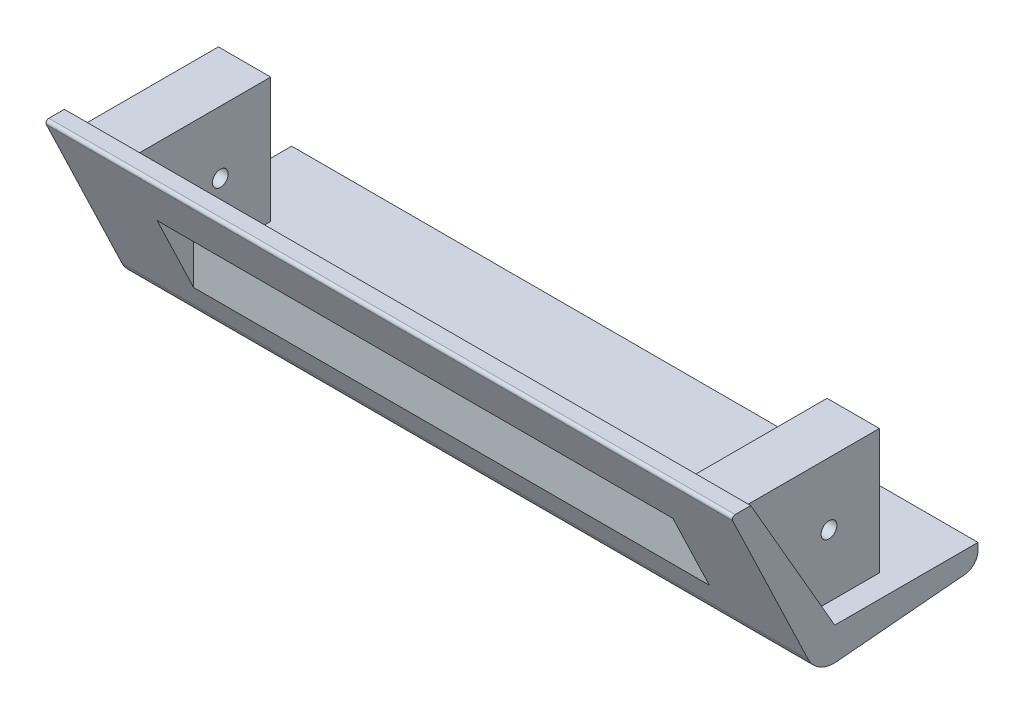
SolidWorks part; units mm, degrees
ref_plane "Front Plane" through (0, 0, 0) normal (0, 0, 1) x (1, 0, 0)
ref_plane "Top Plane" through (0, 0, 0) normal (0, 1, 0) x (1, 0, 0)
ref_plane "Right Plane" through (0, 0, 0) normal (1, 0, 0) x (0, 0, -1)
sketch "Sketch1" plane through (0, 0, 0) normal (1, 0, 0) x (0, 0, -1)
  line L0 (0, 0) -> (-29.3294, 50.8)
  line L1 (0, 0) -> (50, 0)
  line L2 (-29.3294, 50.8) -> (-36.3294, 50.8)
  line L3 (-36.3294, 50.8) -> (-6.2529, -12)
  line L4 (-6.2529, -12) -> (50, -7)
  line L5 (50, -7) -> (50, 0)
  line L6 (-6.2529, -12) -> (-6.2529, 0) construction
  line L7 (-12, 0) -> (0, 0) construction
  dimension "D1" = 50
  dimension "D2" = 60
  dimension "D3" = 50.8
  dimension "D4" = 7
  dimension "D5" = 7
  dimension "D6" = 12
extrude "Boss-Extrude2" add sketch "Sketch1" along normal mid plane 239.55
sketch "Sketch2" plane through (0, 0, 0) normal (0, 0, 1) x (1, 0, 0)
  line L0 (0, 0) -> (0, 50.8) construction
  line L5 (115.75, 47.625) -> (96.7, 47.625) construction
  line L6 (115.75, 47.625) -> (115.75, 3.175) construction
  line L11 (115.75, 3.175) -> (96.7, 3.175) construction
  line L12 (96.7, 47.625) -> (96.7, 3.175) construction
  line L14 (115.35, 47.225) -> (115.35, 3.575)
  line L15 (115.35, 3.575) -> (97.1, 3.575)
  line L28 (97.1, 47.225) -> (97.1, 3.575)
  line L29 (115.35, 47.225) -> (97.1, 47.225)
  line L30 (-96.7, 47.625) -> (-96.7, 3.175) construction
  line L31 (-115.75, 3.175) -> (-96.7, 3.175) construction
  line L32 (-115.75, 47.625) -> (-115.75, 3.175) construction
  line L33 (-115.75, 47.625) -> (-96.7, 47.625) construction
  line L34 (-115.35, 47.225) -> (-97.1, 47.225)
  line L35 (-97.1, 47.225) -> (-97.1, 3.575)
  line L36 (-115.35, 3.575) -> (-97.1, 3.575)
  line L37 (-115.35, 47.225) -> (-115.35, 3.575)
  line L39 (119.775, 0) -> (-119.775, 0) construction
  line L40 (119.775, 50.8) -> (-119.775, 50.8) construction
  line L41 (119.775, 0) -> (119.775, 50.8) construction
  dimension "D2" = 19.05
  dimension "D3" = 44.45
  dimension "D6" = 3.175
  dimension "D4" = 3.175
  dimension "D7" = 4.025
  dimension "D1" = 193.4
  dimension "D5" = 0.4
extrude "Boss-Extrude1" add sketch "Sketch2" along normal up to surface and the other way blind 20 up to face at (0, 25.4, 14.6647)
sketch "Sketch4" plane through (0, 0, 0) normal (1, 0, 0) x (0, 0, -1)
  line L1 (-26.7297, 30.7556) -> (-20, 34.641)
  line L2 (-36.3294, 50.8) -> (-6.2529, -12) construction
  line L3 (0, 0) -> (-29.3294, 50.8) construction
  line L4 (-20, 34.641) -> (-14, 24.2487)
  line L5 (-14, 24.2487) -> (-14, 4.176)
  line L8 (-26.7297, 30.7556) -> (-14, 4.176)
  dimension "D1" = 12
  dimension "D2" = 14
extrude "Cut-Extrude2" cut sketch "Sketch4" against normal mid plane 180
fillet "Fillet1" radius 10 1 edges at (0, -12, 6.2529)
fillet "Fillet2" radius 5 1 edges at (0, -7, -50)
fillet "Fillet3" radius 1 1 edges at (0, 50.8, 36.3294)
hole_wizard "M5 Clearance Hole1" positions "Sketch7" profile "Sketch6" hole size "M5" standard "ANSI Metric" end condition through all
sketch "Sketch7" plane through (115.35, 0, 0) normal (1, 0, 0) x (0, 0, -1)
  line L2 (20, 47.225) -> (20, 3.575) construction
  point P0 (2.4206, 25.4)
  point P14 (20, 25.4)
sketch "Sketch6" plane through (115.35, 25.4, -2.4206) normal (0, 1, 0) x (0, 0, -1)
  line L0 (0, 0) -> (0, 235.125)
  line L1 (0, 235.125) -> (2.75, 235.125)
  line L2 (2.75, 235.125) -> (2.75, 0)
  line L5 (2.75, 0) -> (0, 0)
  line L11 (0, -6.35) -> (0, 107.95) construction
  dimension "Thru Hole Dia." = 5.5
  dimension "Thru Hole Depth" = 235.125
equation "\"D1@Sketch2\"=187.05mm+0.25in"
equation "\"RailSpacing\"= 188.75mm"
equation "\"D1@Boss-Extrude2\"=\"RailSpacing\"+2in"
